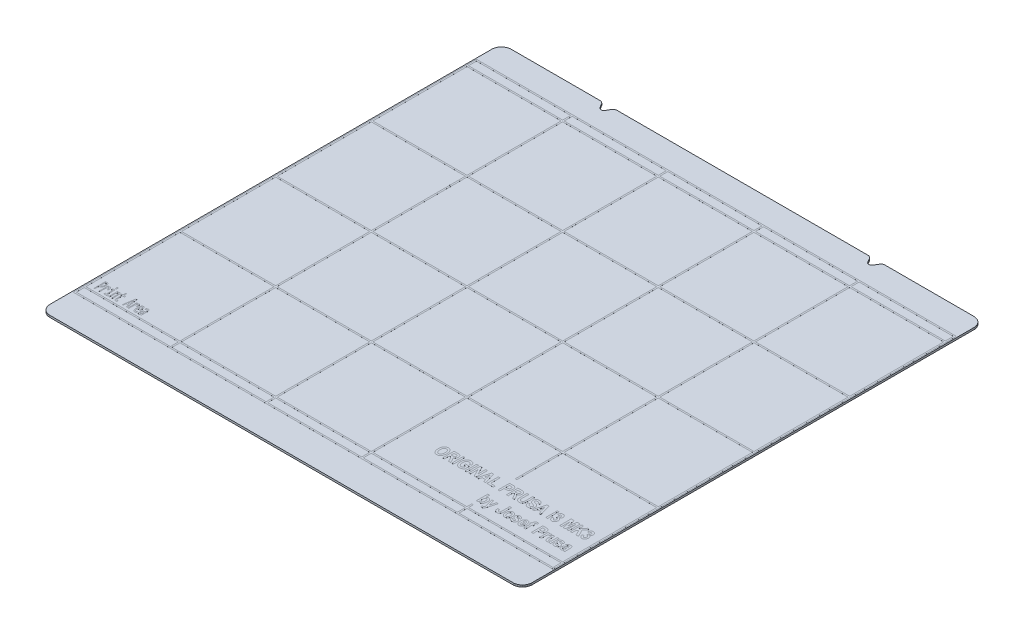
SolidWorks part; units mm, degrees
ref_plane "Front Plane" through (0, 0, 0) normal (0, 0, 1) x (1, 0, 0)
ref_plane "Top Plane" through (0, 0, 0) normal (0, 1, 0) x (1, 0, 0)
ref_plane "Right Plane" through (0, 0, 0) normal (1, 0, 0) x (0, 0, -1)
sketch "Sketch4" plane through (0, 0, 0) normal (0, 1, 0) x (1, 0, 0)
  line L0 (1.1424, 227.1088) -> (1.1396, 17.3082)
  line L1 (251.1473, 227.1078) -> (1.1424, 227.1088)
  line L2 (251.1473, 222.1039) -> (1.1479, 222.1039)
  line L3 (251.1488, 17.1042) -> (1.1424, 17.1042)
  line L4 (251.1488, 22.1065) -> (1.1424, 22.1065)
  line L5 (251.1473, 172.1058) -> (1.1479, 172.1058)
  line L6 (1.1479, 122.1039) -> (251.1473, 122.1039)
  line L7 (251.1488, 72.106) -> (1.1424, 72.106)
  line L8 (101.1481, 227.1078) -> (101.1481, 17.107)
  line L9 (51.1485, 227.1078) -> (51.1485, 17.3082)
  line L10 (151.1473, 17.107) -> (151.1473, 227.1078)
  line L11 (251.1488, 17.1042) -> (251.1473, 227.1078)
  line L12 (201.1482, 17.107) -> (201.1482, 227.1078)
  line L13 (192.2734, 231.2596) -> (192.2734, 234.381)
  line L14 (192.2734, 232.821) -> (194.3544, 232.821)
  line L15 (194.3544, 234.381) -> (194.3544, 231.2596)
  line L16 (196.9752, 231.2596) -> (195.9348, 231.2596)
  line L17 (195.9348, 231.2596) -> (195.4157, 231.7821)
  line L18 (195.4157, 231.7821) -> (195.4157, 232.821)
  line L19 (195.4157, 232.821) -> (195.9348, 233.3417)
  line L20 (195.9348, 233.3417) -> (196.9752, 233.3417)
  line L21 (196.9752, 233.3417) -> (197.4962, 232.821)
  line L22 (197.4962, 232.821) -> (197.4962, 232.3013)
  line L23 (197.4962, 232.3013) -> (195.4157, 232.3013)
  line L24 (199.0771, 233.3417) -> (200.1175, 233.3417)
  line L25 (200.1175, 233.3417) -> (200.6366, 232.821)
  line L26 (200.6366, 232.821) -> (200.6366, 231.2596)
  line L27 (200.6366, 231.2596) -> (199.0771, 231.2596)
  line L28 (199.0771, 231.2596) -> (198.5561, 231.7821)
  line L29 (198.5561, 231.7821) -> (199.0771, 232.3013)
  line L30 (199.0771, 232.3013) -> (200.6366, 232.3013)
  line L31 (202.2175, 233.8614) -> (202.2175, 231.7821)
  line L32 (202.2175, 231.7821) -> (202.7382, 231.2596)
  line L33 (201.6978, 233.3417) -> (202.7382, 233.3417)
  line L34 (203.7913, 234.381) -> (203.7913, 231.2596)
  line L35 (203.7913, 231.2596) -> (205.3526, 231.2596)
  line L36 (205.3526, 231.2596) -> (205.8718, 231.7821)
  line L37 (205.8718, 231.7821) -> (205.8718, 232.821)
  line L38 (205.8718, 232.821) -> (205.3526, 233.3417)
  line L39 (205.3526, 233.3417) -> (203.7913, 233.3417)
  line L40 (208.4931, 231.2596) -> (207.4527, 231.2596)
  line L41 (207.4527, 231.2596) -> (206.933, 231.7821)
  line L42 (206.933, 231.7821) -> (206.933, 232.821)
  line L43 (206.933, 232.821) -> (207.4527, 233.3417)
  line L44 (207.4527, 233.3417) -> (208.4931, 233.3417)
  line L45 (208.4931, 233.3417) -> (209.0138, 232.821)
  line L46 (209.0138, 232.821) -> (209.0138, 232.3013)
  line L47 (209.0138, 232.3013) -> (206.933, 232.3013)
  line L48 (212.1545, 234.381) -> (212.1545, 231.2596)
  line L49 (212.1545, 231.2596) -> (210.5947, 231.2596)
  line L50 (210.5947, 231.2596) -> (210.0735, 231.7821)
  line L51 (210.0735, 231.7821) -> (210.0735, 232.821)
  line L52 (210.0735, 232.821) -> (210.5947, 233.3417)
  line L53 (210.5947, 233.3417) -> (212.1545, 233.3417)
  line L54 (218.4367, 233.8614) -> (217.9163, 234.381)
  line L55 (217.9163, 234.381) -> (216.8759, 234.381)
  line L56 (216.8759, 234.381) -> (216.3562, 233.8614)
  line L57 (216.3562, 233.8614) -> (216.3562, 233.3417)
  line L58 (216.3562, 233.3417) -> (216.8759, 232.821)
  line L59 (216.8759, 232.821) -> (217.9163, 232.821)
  line L60 (217.9163, 232.821) -> (218.4367, 232.3013)
  line L61 (218.4367, 232.3013) -> (218.4367, 231.7821)
  line L62 (218.4367, 231.7821) -> (217.9163, 231.2596)
  line L63 (217.9163, 231.2596) -> (216.8759, 231.2596)
  line L64 (216.8759, 231.2596) -> (216.3562, 231.7821)
  line L65 (220.0176, 233.8614) -> (220.0176, 231.7821)
  line L66 (220.0176, 231.7821) -> (220.5373, 231.2596)
  line L67 (219.4966, 233.3417) -> (220.5373, 233.3417)
  line L68 (223.1514, 231.2596) -> (222.1106, 231.2596)
  line L69 (222.1106, 231.2596) -> (221.5914, 231.7821)
  line L70 (221.5914, 231.7821) -> (221.5914, 232.821)
  line L71 (221.5914, 232.821) -> (222.1106, 233.3417)
  line L72 (222.1106, 233.3417) -> (223.1514, 233.3417)
  line L73 (223.1514, 233.3417) -> (223.6721, 232.821)
  line L74 (223.6721, 232.821) -> (223.6721, 232.3013)
  line L75 (223.6721, 232.3013) -> (221.5914, 232.3013)
  line L76 (226.2932, 231.2596) -> (225.2528, 231.2596)
  line L77 (225.2528, 231.2596) -> (224.7318, 231.7821)
  line L78 (224.7318, 231.7821) -> (224.7318, 232.821)
  line L79 (224.7318, 232.821) -> (225.2528, 233.3417)
  line L80 (225.2528, 233.3417) -> (226.2932, 233.3417)
  line L81 (226.2932, 233.3417) -> (226.8129, 232.821)
  line L82 (226.8129, 232.821) -> (226.8129, 232.3013)
  line L83 (226.8129, 232.3013) -> (224.7318, 232.3013)
  line L84 (227.8736, 234.381) -> (228.3932, 234.381)
  line L85 (228.3932, 234.381) -> (228.3932, 231.2596)
  line L86 (227.8736, 231.2596) -> (228.9142, 231.2596)
  line L87 (235.1898, 233.8614) -> (234.6688, 234.381)
  line L88 (234.6688, 234.381) -> (233.6284, 234.381)
  line L89 (233.6284, 234.381) -> (233.1088, 233.8614)
  line L90 (233.1088, 233.8614) -> (233.1088, 233.3417)
  line L91 (233.1088, 233.3417) -> (233.6284, 232.821)
  line L92 (233.6284, 232.821) -> (234.6688, 232.821)
  line L93 (234.6688, 232.821) -> (235.1898, 232.3013)
  line L94 (235.1898, 232.3013) -> (235.1898, 231.7821)
  line L95 (235.1898, 231.7821) -> (234.6688, 231.2596)
  line L96 (234.6688, 231.2596) -> (233.6284, 231.2596)
  line L97 (233.6284, 231.2596) -> (233.1088, 231.7821)
  line L98 (236.2497, 234.381) -> (236.2497, 231.2596)
  line L99 (236.2497, 232.821) -> (236.7704, 233.3417)
  line L100 (236.7704, 233.3417) -> (237.8108, 233.3417)
  line L101 (237.8108, 233.3417) -> (238.3302, 232.821)
  line L102 (238.3302, 232.821) -> (238.3302, 231.2596)
  line L103 (240.9515, 231.2596) -> (239.9111, 231.2596)
  line L104 (239.9111, 231.2596) -> (239.3902, 231.7821)
  line L105 (239.3902, 231.7821) -> (239.3902, 232.821)
  line L106 (239.3902, 232.821) -> (239.9111, 233.3417)
  line L107 (239.9111, 233.3417) -> (240.9515, 233.3417)
  line L108 (240.9515, 233.3417) -> (241.4722, 232.821)
  line L109 (241.4722, 232.821) -> (241.4722, 232.3013)
  line L110 (241.4722, 232.3013) -> (239.3902, 232.3013)
  line L111 (244.0932, 231.2596) -> (243.0516, 231.2596)
  line L112 (243.0516, 231.2596) -> (242.5319, 231.7821)
  line L113 (242.5319, 231.7821) -> (242.5319, 232.821)
  line L114 (242.5319, 232.821) -> (243.0516, 233.3417)
  line L115 (243.0516, 233.3417) -> (244.0932, 233.3417)
  line L116 (244.0932, 233.3417) -> (244.6129, 232.821)
  line L117 (244.6129, 232.821) -> (244.6129, 232.3013)
  line L118 (244.6129, 232.3013) -> (242.5319, 232.3013)
  line L119 (246.1933, 233.8614) -> (246.1933, 231.7821)
  line L120 (246.1933, 231.7821) -> (246.713, 231.2596)
  line L121 (245.6726, 233.3417) -> (246.713, 233.3417)
  line L122 (10.6674, 28.2237) -> (10.9031, 28.2237)
  line L123 (29.2308, 26.2791) -> (30.7068, 26.2791)
  line L124 (28.7376, 25.7858) -> (29.2308, 26.2791)
  line L125 (29.2308, 25.2953) -> (28.7376, 25.7858)
  line L126 (30.7068, 25.2953) -> (29.2308, 25.2953)
  line L127 (30.7068, 26.7698) -> (30.7068, 25.2953)
  line L128 (30.2148, 27.2646) -> (30.7068, 26.7698)
  line L129 (29.2308, 27.2646) -> (30.2148, 27.2646)
  line L130 (27.7358, 26.2791) -> (25.7665, 26.2791)
  line L131 (27.7358, 26.7698) -> (27.7358, 26.2791)
  line L132 (27.2425, 27.2646) -> (27.7358, 26.7698)
  line L133 (26.2585, 27.2646) -> (27.2425, 27.2646)
  line L134 (25.7665, 26.7698) -> (26.2585, 27.2646)
  line L135 (25.7665, 25.7858) -> (25.7665, 26.7698)
  line L136 (26.2585, 25.2953) -> (25.7665, 25.7858)
  line L137 (27.2425, 25.2953) -> (26.2585, 25.2953)
  line L138 (24.2741, 27.2646) -> (24.7661, 27.2646)
  line L139 (23.2888, 26.2791) -> (24.2741, 27.2646)
  line L140 (23.2888, 25.2953) -> (23.2888, 27.2646)
  line L141 (20.8098, 26.2791) -> (22.287, 26.2791)
  line L142 (20.3178, 25.7858) -> (20.8098, 26.2791)
  line L143 (20.8098, 25.2953) -> (20.3178, 25.7858)
  line L144 (22.287, 25.2953) -> (20.8098, 25.2953)
  line L145 (22.287, 26.7698) -> (22.287, 25.2953)
  line L146 (21.7937, 27.2646) -> (22.287, 26.7698)
  line L147 (20.8098, 27.2646) -> (21.7937, 27.2646)
  line L148 (15.3637, 27.2646) -> (16.3491, 27.2646)
  line L149 (15.8557, 25.7858) -> (16.3491, 25.2953)
  line L150 (15.8557, 27.7551) -> (15.8557, 25.7858)
  line L151 (14.3605, 26.7698) -> (14.3605, 25.2953)
  line L152 (13.8686, 27.2646) -> (14.3605, 26.7698)
  line L153 (12.3913, 27.2646) -> (13.8686, 27.2646)
  line L154 (12.3913, 25.2953) -> (12.3913, 27.2646)
  line L155 (10.4111, 25.2953) -> (11.395, 25.2953)
  line L156 (10.9031, 27.2646) -> (10.9031, 25.2953)
  line L157 (10.4111, 27.2646) -> (10.9031, 27.2646)
  line L158 (8.9187, 27.2646) -> (9.4106, 27.2646)
  line L159 (7.9334, 26.2791) -> (8.9187, 27.2646)
  line L160 (7.9334, 25.2953) -> (7.9334, 27.2646)
  line L161 (6.4382, 26.2791) -> (4.9623, 26.2791)
  line L162 (6.9315, 26.7698) -> (6.4382, 26.2791)
  line L163 (6.9315, 27.7551) -> (6.9315, 26.7698)
  line L164 (6.4382, 28.2484) -> (6.9315, 27.7551)
  line L165 (4.9623, 28.2484) -> (6.4382, 28.2484)
  line L166 (4.9623, 25.2953) -> (4.9623, 28.2484)
  line L167 (199.8955, 5.1442) -> (199.8955, 5.3371)
  line L168 (199.8955, 5.3371) -> (199.7438, 5.9118)
  line L169 (199.7438, 5.9118) -> (199.3483, 6.4589)
  line L170 (199.3483, 6.4589) -> (198.7875, 6.7869)
  line L171 (198.7875, 6.7869) -> (198.1454, 6.8971)
  line L172 (198.1454, 6.8971) -> (197.502, 6.7869)
  line L173 (197.502, 6.7869) -> (196.9409, 6.4589)
  line L174 (196.9409, 6.4589) -> (196.5455, 5.9118)
  line L175 (196.5455, 5.9118) -> (196.3953, 5.3371)
  line L176 (196.3953, 5.3371) -> (196.3953, 5.1442)
  line L177 (196.3953, 5.1442) -> (196.3953, 4.9747)
  line L178 (196.3953, 4.9747) -> (196.5317, 4.4634)
  line L179 (196.5317, 4.4634) -> (196.9079, 3.9081)
  line L180 (196.9079, 3.9081) -> (197.4632, 3.5333)
  line L181 (197.4632, 3.5333) -> (197.9747, 3.3955)
  line L182 (197.9747, 3.3955) -> (198.1454, 3.3955)
  line L183 (198.1454, 3.3955) -> (198.3148, 3.3955)
  line L184 (198.3148, 3.3955) -> (198.8264, 3.5333)
  line L185 (198.8264, 3.5333) -> (199.3816, 3.9081)
  line L186 (199.3816, 3.9081) -> (199.7575, 4.4634)
  line L187 (199.7575, 4.4634) -> (199.8955, 4.9747)
  line L188 (199.8955, 4.9747) -> (199.8955, 5.1442)
  line L189 (54.3951, 5.1442) -> (54.3951, 5.3151)
  line L190 (54.3951, 5.3151) -> (54.2574, 5.8277)
  line L191 (54.2574, 5.8277) -> (53.8825, 6.3831)
  line L192 (53.8825, 6.3831) -> (53.3258, 6.7579)
  line L193 (53.3258, 6.7579) -> (52.8147, 6.8943)
  line L194 (52.8147, 6.8943) -> (52.6451, 6.8943)
  line L195 (52.6451, 6.8943) -> (52.4744, 6.8943)
  line L196 (52.4744, 6.8943) -> (51.9631, 6.7579)
  line L197 (51.9631, 6.7579) -> (51.4078, 6.3831)
  line L198 (51.4078, 6.3831) -> (51.0314, 5.8277)
  line L199 (51.0314, 5.8277) -> (50.8953, 5.3151)
  line L200 (50.8953, 5.3151) -> (50.8953, 5.1442)
  line L201 (50.8953, 5.1442) -> (50.8953, 4.9747)
  line L202 (50.8953, 4.9747) -> (51.0314, 4.4634)
  line L203 (51.0314, 4.4634) -> (51.4078, 3.9081)
  line L204 (51.4078, 3.9081) -> (51.9631, 3.5333)
  line L205 (51.9631, 3.5333) -> (52.4744, 3.3955)
  line L206 (52.4744, 3.3955) -> (52.6451, 3.3955)
  line L207 (52.6451, 3.3955) -> (52.8147, 3.3955)
  line L208 (52.8147, 3.3955) -> (53.3258, 3.5333)
  line L209 (53.3258, 3.5333) -> (53.8825, 3.9081)
  line L210 (53.8825, 3.9081) -> (54.2574, 4.4634)
  line L211 (54.2574, 4.4634) -> (54.3951, 4.9747)
  line L212 (54.3951, 4.9747) -> (54.3951, 5.1442)
  line L213 (0.1461, 5.1442) -> (0.1461, 4.8934)
  line L214 (0.1461, 4.8934) -> (0.2467, 4.1383)
  line L215 (0.2467, 4.1383) -> (0.5388, 3.1998)
  line L216 (0.5388, 3.1998) -> (0.9991, 2.3496)
  line L217 (0.9991, 2.3496) -> (1.6095, 1.6095)
  line L218 (1.6095, 1.6095) -> (2.3496, 0.9991)
  line L219 (2.3496, 0.9991) -> (3.1984, 0.5388)
  line L220 (3.1984, 0.5388) -> (4.1369, 0.2467)
  line L221 (4.1369, 0.2467) -> (4.8934, 0.1447)
  line L222 (4.8934, 0.1447) -> (5.1456, 0.1447)
  line L223 (247.1456, 0.1447) -> (5.1456, 0.1447)
  line L224 (247.1456, 0.1447) -> (247.3963, 0.1447)
  line L225 (247.3963, 0.1447) -> (248.1532, 0.2467)
  line L226 (248.1532, 0.2467) -> (249.0914, 0.5388)
  line L227 (249.0914, 0.5388) -> (249.9403, 0.9991)
  line L228 (249.9403, 0.9991) -> (250.6805, 1.6095)
  line L229 (250.6805, 1.6095) -> (251.2906, 2.3496)
  line L230 (251.2906, 2.3496) -> (251.7511, 3.1998)
  line L231 (251.7511, 3.1998) -> (252.0432, 4.1383)
  line L232 (252.0432, 4.1383) -> (252.145, 4.8934)
  line L233 (252.145, 4.8934) -> (252.145, 5.1442)
  line L234 (252.145, 236.1448) -> (252.145, 5.1442)
  line L235 (252.145, 236.1448) -> (252.145, 236.6244)
  line L236 (252.145, 236.6244) -> (251.7648, 238.059)
  line L237 (251.7648, 238.059) -> (250.9159, 239.4466)
  line L238 (250.9159, 239.4466) -> (250.6817, 239.6807)
  line L239 (250.6817, 239.6807) -> (250.446, 239.9165)
  line L240 (250.446, 239.9165) -> (249.0582, 240.7651)
  line L241 (249.0582, 240.7651) -> (247.6238, 241.1458)
  line L242 (247.6238, 241.1458) -> (247.1456, 241.1458)
  line L243 (0.1461, 5.1442) -> (0.1461, 236.1448)
  line L244 (5.1456, 241.1458) -> (4.6661, 241.1458)
  line L245 (4.6661, 241.1458) -> (3.2315, 240.7651)
  line L246 (3.2315, 240.7651) -> (1.8438, 239.9165)
  line L247 (1.8438, 239.9165) -> (1.6095, 239.6807)
  line L248 (1.6095, 239.6807) -> (1.3753, 239.4466)
  line L249 (1.3753, 239.4466) -> (0.5264, 238.059)
  line L250 (0.5264, 238.059) -> (0.1461, 236.6244)
  line L251 (0.1461, 236.6244) -> (0.1461, 236.1448)
  line L252 (194.8437, 237.9017) -> (194.9371, 237.7361)
  line L253 (194.9371, 237.7361) -> (195.403, 237.3394)
  line L254 (195.403, 237.3394) -> (196.1279, 237.1453)
  line L255 (196.1279, 237.1453) -> (196.8556, 237.3231)
  line L256 (196.8556, 237.3231) -> (197.3308, 237.7074)
  line L257 (197.3308, 237.7074) -> (197.4304, 237.8713)
  line L258 (54.8612, 237.8713) -> (54.959, 237.7087)
  line L259 (54.959, 237.7087) -> (55.4345, 237.3231)
  line L260 (55.4345, 237.3231) -> (56.1619, 237.1453)
  line L261 (56.1619, 237.1453) -> (56.8869, 237.3394)
  line L262 (56.8869, 237.3394) -> (57.3524, 237.7361)
  line L263 (57.3524, 237.7361) -> (57.4477, 237.9017)
  line L264 (5.1456, 241.1458) -> (51.7578, 241.1458)
  line L265 (54.8612, 237.8713) -> (53.4706, 240.1781)
  line L266 (53.4706, 240.1781) -> (53.3799, 240.3285)
  line L267 (53.3799, 240.3285) -> (52.7416, 240.888)
  line L268 (52.7416, 240.888) -> (52.0029, 241.1458)
  line L269 (52.0029, 241.1458) -> (51.7578, 241.1458)
  line L270 (57.4477, 237.9017) -> (58.7251, 240.1369)
  line L271 (60.4614, 241.1458) -> (60.2092, 241.1458)
  line L272 (60.2092, 241.1458) -> (59.4568, 240.8756)
  line L273 (59.4568, 240.8756) -> (58.8134, 240.2929)
  line L274 (58.8134, 240.2929) -> (58.7251, 240.1369)
  line L275 (194.8437, 237.9017) -> (193.566, 240.1369)
  line L276 (60.4614, 241.1458) -> (191.8299, 241.1458)
  line L277 (193.566, 240.1369) -> (193.4766, 240.2929)
  line L278 (193.4766, 240.2929) -> (192.833, 240.8756)
  line L279 (192.833, 240.8756) -> (192.0804, 241.1458)
  line L280 (192.0804, 241.1458) -> (191.8299, 241.1458)
  line L281 (200.5333, 241.1458) -> (247.1456, 241.1458)
  line L282 (197.4304, 237.8713) -> (198.8205, 240.1781)
  line L283 (200.5333, 241.1458) -> (200.2869, 241.1458)
  line L284 (200.2869, 241.1458) -> (199.548, 240.888)
  line L285 (199.548, 240.888) -> (198.9102, 240.3285)
  line L286 (198.9102, 240.3285) -> (198.8205, 240.1781)
extrude "Boss-Extrude2" add sketch "Sketch4" along normal blind 1 contours L223 L222 L221 L220 L219 L218 L217 L216 L215 L214 L213 L243 L251 L250 L249 L248 L247 L246 L245 L244 L264 L269 L268 L267 L266 L265 L258 L259 L260 L261 L262 L263 L270 L274 L273 L272 L271 L276 L280 L279 L278 L277 L275 L252 L253 L254 L255 L256 L257 L282 L286 L285 L284 L283 L281 L242 L241 L240 L239 L238 L237 L236 L235 L234 L233 L232 L231 L230 L229 L228 L227 L226 L225 L224
sketch "Sketch6" plane through (0, 1, 1) normal (0, 1, 0) x (1, 0, 0)
  line L0 (1.1424, 228.1088) -> (1.1396, 18.3082) construction
  line L1 (251.1473, 228.1078) -> (1.1424, 228.1088) construction
  line L2 (200.7482, 48.7971) -> (200.7482, 72.706)
  line L3 (251.1488, 18.1042) -> (1.1424, 18.1042) construction
  line L4 (251.1488, 23.1065) -> (1.1424, 23.1065) construction
  line L5 (151.5473, 173.5058) -> (151.5473, 222.7039)
  line L6 (1.1479, 123.1039) -> (151.1473, 123.1039) construction
  line L7 (251.1488, 73.106) -> (1.1424, 73.106) construction
  line L8 (100.7481, 227.7084) -> (51.5485, 227.7086)
  line L9 (100.7481, 223.5039) -> (51.5485, 223.5039)
  line L10 (151.1473, 18.107) -> (151.1473, 73.106) construction
  line L11 (251.1488, 18.1042) -> (251.1473, 228.1078) construction
  line L12 (201.1482, 18.107) -> (201.1482, 73.106) construction
  line L13 (192.2734, 232.2596) -> (192.2734, 235.381)
  line L14 (192.2734, 233.821) -> (194.3544, 233.821)
  line L15 (194.3544, 235.381) -> (194.3544, 232.2596)
  line L16 (196.9752, 232.2596) -> (195.9348, 232.2596)
  line L17 (195.9348, 232.2596) -> (195.4157, 232.7821)
  line L18 (195.4157, 232.7821) -> (195.4157, 233.821)
  line L19 (195.4157, 233.821) -> (195.9348, 234.3417)
  line L20 (195.9348, 234.3417) -> (196.9752, 234.3417)
  line L21 (196.9752, 234.3417) -> (197.4962, 233.821)
  line L22 (197.4962, 233.821) -> (197.4962, 233.3013)
  line L23 (197.4962, 233.3013) -> (195.4157, 233.3013)
  line L24 (199.0771, 234.3417) -> (200.1175, 234.3417)
  line L25 (200.1175, 234.3417) -> (200.6366, 233.821)
  line L26 (200.6366, 233.821) -> (200.6366, 232.2596)
  line L27 (200.6366, 232.2596) -> (199.0771, 232.2596)
  line L28 (199.0771, 232.2596) -> (198.5561, 232.7821)
  line L29 (198.5561, 232.7821) -> (199.0771, 233.3013)
  line L30 (199.0771, 233.3013) -> (200.6366, 233.3013)
  line L31 (202.2175, 234.8614) -> (202.2175, 232.7821)
  line L32 (202.2175, 232.7821) -> (202.7382, 232.2596)
  line L33 (201.6978, 234.3417) -> (202.7382, 234.3417)
  line L34 (203.7913, 235.381) -> (203.7913, 232.2596)
  line L35 (203.7913, 232.2596) -> (205.3526, 232.2596)
  line L36 (205.3526, 232.2596) -> (205.8718, 232.7821)
  line L37 (205.8718, 232.7821) -> (205.8718, 233.821)
  line L38 (205.8718, 233.821) -> (205.3526, 234.3417)
  line L39 (205.3526, 234.3417) -> (203.7913, 234.3417)
  line L40 (208.4931, 232.2596) -> (207.4527, 232.2596)
  line L41 (207.4527, 232.2596) -> (206.933, 232.7821)
  line L42 (206.933, 232.7821) -> (206.933, 233.821)
  line L43 (206.933, 233.821) -> (207.4527, 234.3417)
  line L44 (207.4527, 234.3417) -> (208.4931, 234.3417)
  line L45 (208.4931, 234.3417) -> (209.0138, 233.821)
  line L46 (209.0138, 233.821) -> (209.0138, 233.3013)
  line L47 (209.0138, 233.3013) -> (206.933, 233.3013)
  line L48 (212.1545, 235.381) -> (212.1545, 232.2596)
  line L49 (212.1545, 232.2596) -> (210.5947, 232.2596)
  line L50 (210.5947, 232.2596) -> (210.0735, 232.7821)
  line L51 (210.0735, 232.7821) -> (210.0735, 233.821)
  line L52 (210.0735, 233.821) -> (210.5947, 234.3417)
  line L53 (210.5947, 234.3417) -> (212.1545, 234.3417)
  line L54 (218.4367, 234.8614) -> (217.9163, 235.381)
  line L55 (217.9163, 235.381) -> (216.8759, 235.381)
  line L56 (216.8759, 235.381) -> (216.3562, 234.8614)
  line L57 (216.3562, 234.8614) -> (216.3562, 234.3417)
  line L58 (216.3562, 234.3417) -> (216.8759, 233.821)
  line L59 (216.8759, 233.821) -> (217.9163, 233.821)
  line L60 (217.9163, 233.821) -> (218.4367, 233.3013)
  line L61 (218.4367, 233.3013) -> (218.4367, 232.7821)
  line L62 (218.4367, 232.7821) -> (217.9163, 232.2596)
  line L63 (217.9163, 232.2596) -> (216.8759, 232.2596)
  line L64 (216.8759, 232.2596) -> (216.3562, 232.7821)
  line L65 (220.0176, 234.8614) -> (220.0176, 232.7821)
  line L66 (220.0176, 232.7821) -> (220.5373, 232.2596)
  line L67 (219.4966, 234.3417) -> (220.5373, 234.3417)
  line L68 (223.1514, 232.2596) -> (222.1106, 232.2596)
  line L69 (222.1106, 232.2596) -> (221.5914, 232.7821)
  line L70 (221.5914, 232.7821) -> (221.5914, 233.821)
  line L71 (221.5914, 233.821) -> (222.1106, 234.3417)
  line L72 (222.1106, 234.3417) -> (223.1514, 234.3417)
  line L73 (223.1514, 234.3417) -> (223.6721, 233.821)
  line L74 (223.6721, 233.821) -> (223.6721, 233.3013)
  line L75 (223.6721, 233.3013) -> (221.5914, 233.3013)
  line L76 (226.2932, 232.2596) -> (225.2528, 232.2596)
  line L77 (225.2528, 232.2596) -> (224.7318, 232.7821)
  line L78 (224.7318, 232.7821) -> (224.7318, 233.821)
  line L79 (224.7318, 233.821) -> (225.2528, 234.3417)
  line L80 (225.2528, 234.3417) -> (226.2932, 234.3417)
  line L81 (226.2932, 234.3417) -> (226.8129, 233.821)
  line L82 (226.8129, 233.821) -> (226.8129, 233.3013)
  line L83 (226.8129, 233.3013) -> (224.7318, 233.3013)
  line L84 (227.8736, 235.381) -> (228.3932, 235.381)
  line L85 (228.3932, 235.381) -> (228.3932, 232.2596)
  line L86 (227.8736, 232.2596) -> (228.9142, 232.2596)
  line L87 (235.1898, 234.8614) -> (234.6688, 235.381)
  line L88 (234.6688, 235.381) -> (233.6284, 235.381)
  line L89 (233.6284, 235.381) -> (233.1088, 234.8614)
  line L90 (233.1088, 234.8614) -> (233.1088, 234.3417)
  line L91 (233.1088, 234.3417) -> (233.6284, 233.821)
  line L92 (233.6284, 233.821) -> (234.6688, 233.821)
  line L93 (234.6688, 233.821) -> (235.1898, 233.3013)
  line L94 (235.1898, 233.3013) -> (235.1898, 232.7821)
  line L95 (235.1898, 232.7821) -> (234.6688, 232.2596)
  line L96 (234.6688, 232.2596) -> (233.6284, 232.2596)
  line L97 (233.6284, 232.2596) -> (233.1088, 232.7821)
  line L98 (236.2497, 235.381) -> (236.2497, 232.2596)
  line L99 (236.2497, 233.821) -> (236.7704, 234.3417)
  line L100 (236.7704, 234.3417) -> (237.8108, 234.3417)
  line L101 (237.8108, 234.3417) -> (238.3302, 233.821)
  line L102 (238.3302, 233.821) -> (238.3302, 232.2596)
  line L103 (240.9515, 232.2596) -> (239.9111, 232.2596)
  line L104 (239.9111, 232.2596) -> (239.3902, 232.7821)
  line L105 (239.3902, 232.7821) -> (239.3902, 233.821)
  line L106 (239.3902, 233.821) -> (239.9111, 234.3417)
  line L107 (239.9111, 234.3417) -> (240.9515, 234.3417)
  line L108 (240.9515, 234.3417) -> (241.4722, 233.821)
  line L109 (241.4722, 233.821) -> (241.4722, 233.3013)
  line L110 (241.4722, 233.3013) -> (239.3902, 233.3013)
  line L111 (244.0932, 232.2596) -> (243.0516, 232.2596)
  line L112 (243.0516, 232.2596) -> (242.5319, 232.7821)
  line L113 (242.5319, 232.7821) -> (242.5319, 233.821)
  line L114 (242.5319, 233.821) -> (243.0516, 234.3417)
  line L115 (243.0516, 234.3417) -> (244.0932, 234.3417)
  line L116 (244.0932, 234.3417) -> (244.6129, 233.821)
  line L117 (244.6129, 233.821) -> (244.6129, 233.3013)
  line L118 (244.6129, 233.3013) -> (242.5319, 233.3013)
  line L119 (246.1933, 234.8614) -> (246.1933, 232.7821)
  line L120 (246.1933, 232.7821) -> (246.713, 232.2596)
  line L121 (245.6726, 234.3417) -> (246.713, 234.3417)
  line L122 (10.6674, 29.2237) -> (10.9031, 29.2237)
  line L123 (29.2308, 27.2791) -> (30.7068, 27.2791)
  line L124 (28.7376, 26.7858) -> (29.2308, 27.2791)
  line L125 (29.2308, 26.2953) -> (28.7376, 26.7858)
  line L126 (30.7068, 26.2953) -> (29.2308, 26.2953)
  line L127 (30.7068, 27.7698) -> (30.7068, 26.2953)
  line L128 (30.2148, 28.2646) -> (30.7068, 27.7698)
  line L129 (29.2308, 28.2646) -> (30.2148, 28.2646)
  line L130 (27.7358, 27.2791) -> (25.7665, 27.2791)
  line L131 (27.7358, 27.7698) -> (27.7358, 27.2791)
  line L132 (27.2425, 28.2646) -> (27.7358, 27.7698)
  line L133 (26.2585, 28.2646) -> (27.2425, 28.2646)
  line L134 (25.7665, 27.7698) -> (26.2585, 28.2646)
  line L135 (25.7665, 26.7858) -> (25.7665, 27.7698)
  line L136 (26.2585, 26.2953) -> (25.7665, 26.7858)
  line L137 (27.2425, 26.2953) -> (26.2585, 26.2953)
  line L138 (24.2741, 28.2646) -> (24.7661, 28.2646)
  line L139 (23.2888, 27.2791) -> (24.2741, 28.2646)
  line L140 (23.2888, 26.2953) -> (23.2888, 28.2646)
  line L141 (20.8098, 27.2791) -> (22.287, 27.2791)
  line L142 (20.3178, 26.7858) -> (20.8098, 27.2791)
  line L143 (20.8098, 26.2953) -> (20.3178, 26.7858)
  line L144 (22.287, 26.2953) -> (20.8098, 26.2953)
  line L145 (22.287, 27.7698) -> (22.287, 26.2953)
  line L146 (21.7937, 28.2646) -> (22.287, 27.7698)
  line L147 (20.8098, 28.2646) -> (21.7937, 28.2646)
  line L148 (15.3637, 28.2646) -> (16.3491, 28.2646)
  line L149 (15.8557, 26.7858) -> (16.3491, 26.2953)
  line L150 (15.8557, 28.7551) -> (15.8557, 26.7858)
  line L151 (14.3605, 27.7698) -> (14.3605, 26.2953)
  line L152 (13.8686, 28.2646) -> (14.3605, 27.7698)
  line L153 (12.3913, 28.2646) -> (13.8686, 28.2646)
  line L154 (12.3913, 26.2953) -> (12.3913, 28.2646)
  line L155 (10.4111, 26.2953) -> (11.395, 26.2953)
  line L156 (10.9031, 28.2646) -> (10.9031, 26.2953)
  line L157 (10.4111, 28.2646) -> (10.9031, 28.2646)
  line L158 (8.9187, 28.2646) -> (9.4106, 28.2646)
  line L159 (7.9334, 27.2791) -> (8.9187, 28.2646)
  line L160 (7.9334, 26.2953) -> (7.9334, 28.2646)
  line L161 (6.4382, 27.2791) -> (4.9623, 27.2791)
  line L162 (6.9315, 27.7698) -> (6.4382, 27.2791)
  line L163 (6.9315, 28.7551) -> (6.9315, 27.7698)
  line L164 (6.4382, 29.2484) -> (6.9315, 28.7551)
  line L165 (4.9623, 29.2484) -> (6.4382, 29.2484)
  line L166 (4.9623, 26.2953) -> (4.9623, 29.2484)
  line L287 (0.7424, 228.5088) -> (0.7396, 18.3082)
  line L288 (251.5473, 228.5077) -> (0.7424, 228.5088)
  line L289 (251.5489, 17.7042) -> (251.5473, 228.5077)
  line L290 (251.5489, 17.7042) -> (1.1424, 17.7042)
  line L291 (250.7488, 22.7065) -> (201.5482, 22.7065)
  line L292 (51.5485, 227.7086) -> (51.5485, 223.5039)
  line L293 (101.5481, 227.7084) -> (101.5481, 223.5039)
  line L294 (251.1488, 72.706) -> (251.1485, 72.706)
  line L295 (150.7473, 18.5042) -> (150.7473, 22.7065)
  line L296 (200.7482, 18.5042) -> (200.7482, 22.7065)
  line L297 (1.541, 123.5039) -> (50.7485, 123.5039)
  line L298 (250.7477, 172.7058) -> (201.5482, 172.7058)
  line L299 (250.7474, 222.7039) -> (201.5482, 222.7039)
  line L300 (1.5424, 227.7088) -> (1.5423, 223.5039)
  line L301 (250.7473, 227.7078) -> (201.5482, 227.708)
  line L302 (250.7488, 18.5042) -> (250.7488, 22.7065)
  line L303 (250.7488, 18.5042) -> (201.5482, 18.5042)
  line L304 (250.7488, 23.5065) -> (201.5482, 23.5065)
  line L305 (50.7485, 227.7086) -> (50.7485, 223.5039)
  line L306 (100.7481, 227.7084) -> (100.7481, 223.5039)
  line L307 (251.1488, 73.506) -> (251.1484, 73.506)
  line L308 (151.5473, 18.5042) -> (151.5473, 22.7065)
  line L309 (201.5482, 18.5042) -> (201.5482, 22.7065)
  line L310 (1.541, 122.7039) -> (50.7485, 122.7039)
  line L311 (250.7477, 173.5058) -> (201.5482, 173.5058)
  line L312 (250.7474, 223.5039) -> (201.5482, 223.504)
  line L313 (0.7396, 18.3082) -> (0.7396, 17.7042)
  line L314 (0.7396, 17.7042) -> (1.1424, 17.7042)
  line L315 (1.5397, 22.7065) -> (1.5396, 18.5042)
  line L316 (50.7485, 18.5042) -> (1.5396, 18.5042)
  line L317 (1.5424, 227.7088) -> (1.5396, 18.3082) construction
  line L318 (251.1488, 22.7065) -> (1.1424, 22.7065) construction
  line L319 (251.1488, 23.5065) -> (1.1424, 23.5065) construction
  line L320 (250.7488, 18.5042) -> (1.1424, 18.5042) construction
  line L321 (50.7485, 22.7065) -> (1.5397, 22.7065)
  line L322 (101.5481, 222.7039) -> (101.5481, 173.5058)
  line L323 (150.7473, 227.7082) -> (101.5481, 227.7084)
  line L324 (51.5485, 22.7065) -> (51.5485, 18.5042)
  line L325 (50.7485, 23.5065) -> (1.5397, 23.5065)
  line L326 (50.7485, 22.7065) -> (50.7485, 18.5042)
  line L327 (100.7481, 23.5065) -> (51.5485, 23.5065)
  line L328 (100.7481, 22.7065) -> (100.7481, 18.5042)
  line L329 (100.7481, 22.7065) -> (51.5485, 22.7065)
  line L330 (200.7482, 227.708) -> (151.5473, 227.7082)
  line L331 (101.5481, 22.7065) -> (101.5481, 18.5042)
  line L332 (100.7481, 18.5042) -> (51.5485, 18.5042)
  line L333 (151.5473, 223.5039) -> (151.5473, 227.7082)
  line L334 (150.7473, 18.5042) -> (101.5481, 18.5042)
  line L335 (150.7473, 23.5065) -> (150.7473, 72.706)
  line L336 (151.5473, 18.107) -> (151.5473, 228.1078) construction
  line L337 (150.7473, 18.107) -> (150.7473, 228.1078) construction
  line L338 (150.7473, 23.5065) -> (101.5481, 23.5065)
  line L339 (151.5473, 23.5065) -> (151.5473, 72.706)
  line L340 (150.7473, 22.7065) -> (101.5481, 22.7065)
  line L341 (200.7482, 18.5042) -> (151.5473, 18.5042)
  line L342 (200.7482, 23.5065) -> (151.5473, 23.5065)
  line L343 (200.7482, 18.107) -> (200.7482, 228.1078) construction
  line L344 (201.5482, 18.107) -> (201.5482, 228.1078) construction
  line L345 (200.7482, 23.5065) -> (200.7482, 26.0065)
  line L346 (200.7482, 22.7065) -> (151.5473, 22.7065)
  line L347 (201.5482, 23.5065) -> (201.5482, 26.0065)
  line L348 (250.7488, 23.5065) -> (250.7485, 72.706)
  line L349 (250.7484, 73.506) -> (201.5482, 73.506)
  line L350 (250.7488, 18.5042) -> (250.7473, 227.7078) construction
  line L351 (250.7484, 73.506) -> (250.7481, 122.7039)
  line L352 (251.1488, 73.506) -> (1.1424, 73.506) construction
  line L353 (250.7485, 72.706) -> (201.5482, 72.706)
  line L354 (200.7482, 73.506) -> (151.5473, 73.506)
  line L355 (251.1488, 72.706) -> (1.1424, 72.706) construction
  line L356 (201.5482, 73.506) -> (201.5482, 122.7039)
  line L357 (200.7482, 72.706) -> (151.5473, 72.706)
  line L358 (200.7482, 73.506) -> (200.7482, 122.7039)
  line L359 (150.7473, 73.506) -> (150.7473, 122.7039)
  line L360 (150.7473, 73.506) -> (101.5481, 73.506)
  line L361 (151.5473, 73.506) -> (151.5473, 122.7039)
  line L362 (150.7473, 72.706) -> (101.5481, 72.706)
  line L363 (101.5481, 72.706) -> (101.5481, 23.5065)
  line L364 (100.7481, 73.506) -> (51.5485, 73.506)
  line L365 (100.7481, 72.706) -> (100.7481, 23.5065)
  line L366 (100.7481, 72.706) -> (51.5485, 72.706)
  line L367 (51.5485, 72.706) -> (51.5485, 23.5065)
  line L368 (50.7485, 73.506) -> (1.5404, 73.506)
  line L369 (50.7485, 72.706) -> (50.7485, 23.5065)
  line L370 (50.7485, 72.706) -> (1.5404, 72.706)
  line L371 (1.5404, 72.706) -> (1.5397, 23.5065)
  line L372 (1.541, 122.7039) -> (1.5404, 73.506)
  line L373 (1.1479, 123.5039) -> (251.1473, 123.5039) construction
  line L374 (51.5485, 123.5039) -> (100.7481, 123.5039)
  line L375 (1.1479, 122.7039) -> (251.1473, 122.7039) construction
  line L376 (50.7485, 122.7039) -> (50.7485, 73.506)
  line L377 (51.5485, 122.7039) -> (100.7481, 122.7039)
  line L378 (51.5485, 122.7039) -> (51.5485, 73.506)
  line L379 (101.5481, 123.5039) -> (150.7473, 123.5039)
  line L380 (101.5481, 122.7039) -> (101.5481, 73.506)
  line L381 (101.5481, 122.7039) -> (150.7473, 122.7039)
  line L382 (100.7481, 122.7039) -> (100.7481, 73.506)
  line L383 (150.7473, 123.5039) -> (150.7473, 172.7058)
  line L384 (151.5473, 122.7039) -> (200.7482, 122.7039)
  line L385 (151.1473, 122.7039) -> (151.1473, 123.1039) construction
  line L386 (151.1473, 18.107) -> (151.1473, 228.1078) construction
  line L387 (151.5473, 123.5039) -> (151.5473, 172.7058)
  line L388 (200.7482, 123.1039) -> (201.5482, 123.1039) construction
  line L389 (1.1479, 123.1039) -> (251.1473, 123.1039) construction
  line L390 (151.5473, 123.5039) -> (200.7482, 123.5039)
  line L391 (101.5481, 172.7058) -> (101.5481, 123.5039)
  line L392 (201.5482, 123.5039) -> (250.7481, 123.5039)
  line L393 (201.5482, 123.5039) -> (201.5482, 172.7058)
  line L394 (200.7482, 223.5039) -> (151.5473, 223.5039)
  line L395 (201.5482, 122.7039) -> (250.7481, 122.7039)
  line L396 (201.1482, 122.7039) -> (201.1482, 123.1039) construction
  line L397 (201.1482, 18.107) -> (201.1482, 228.1078) construction
  line L398 (200.7482, 123.5039) -> (200.7482, 172.7058)
  line L399 (250.7481, 123.5039) -> (250.7477, 172.7058)
  line L400 (150.7473, 173.5058) -> (150.7473, 222.7039)
  line L401 (51.5485, 172.7058) -> (51.5485, 123.5039)
  line L402 (150.7473, 173.5058) -> (101.5481, 173.5058)
  line L403 (250.7477, 173.5058) -> (250.7474, 222.7039)
  line L404 (201.5482, 173.5058) -> (201.5482, 222.7039)
  line L405 (200.7482, 173.5058) -> (151.5473, 173.5058)
  line L406 (250.7474, 223.5039) -> (250.7473, 227.7078)
  line L407 (200.7482, 173.5058) -> (200.7482, 222.7039)
  line L408 (51.1485, 123.1039) -> (51.1485, 18.3082) construction
  line L409 (200.7482, 172.7058) -> (151.5473, 172.7058)
  line L410 (150.7473, 172.7058) -> (101.5481, 172.7058)
  line L411 (100.7481, 173.5058) -> (51.5485, 173.5058)
  line L412 (50.7485, 173.5058) -> (1.5417, 173.5058)
  line L413 (150.7473, 223.5039) -> (101.5481, 223.5039)
  line L414 (100.7481, 172.7058) -> (100.7481, 123.5039)
  line L415 (1.5417, 172.7058) -> (1.541, 123.5039)
  line L416 (100.7481, 172.7058) -> (51.5485, 172.7058)
  line L417 (101.1481, 123.1039) -> (101.1481, 18.107) construction
  line L418 (100.7481, 222.7039) -> (51.5485, 222.7039)
  line L419 (50.7485, 172.7058) -> (50.7485, 123.5039)
  line L420 (50.7485, 227.7086) -> (1.5424, 227.7088)
  line L421 (50.7485, 172.7058) -> (1.5417, 172.7058)
  line L422 (200.7482, 48.7971) -> (201.5482, 48.7971)
  line L424 (201.5482, 48.7971) -> (201.5482, 72.706)
  line L425 (1.5423, 222.7039) -> (1.5417, 173.5058)
  line L426 (250.7473, 227.7078) -> (1.5424, 227.7088) construction
  line L427 (50.7485, 223.5039) -> (1.5423, 223.5039)
  line L428 (50.7485, 222.7039) -> (1.5423, 222.7039)
  line L429 (51.5485, 222.7039) -> (51.5485, 173.5058)
  line L430 (50.7485, 222.7039) -> (50.7485, 173.5058)
  line L431 (150.7473, 223.5039) -> (150.7473, 227.7082)
  line L432 (100.7481, 222.7039) -> (100.7481, 173.5058)
  line L433 (150.7473, 222.7039) -> (101.5481, 222.7039)
  line L434 (201.5482, 223.504) -> (201.5482, 227.708)
  line L436 (200.7482, 223.5039) -> (200.7482, 227.708)
  line L437 (200.7482, 222.7039) -> (151.5473, 222.7039)
  line L438 (200.7482, 26.0065) -> (201.5482, 26.0065)
  point P268 (51.5485, 228.1078)
  point P269 (51.5485, 18.3082)
  point P270 (101.5481, 228.1078)
  point P271 (101.5481, 18.107)
  point P291 (50.7485, 228.1078)
  point P292 (50.7485, 18.3082)
  point P293 (100.7481, 228.1078)
  point P294 (100.7481, 18.107)
  dimension "D1" = 0.4
  dimension "D3" = 2.5
  dimension "D2" = 0.4
extrude "Boss-Extrude5" add sketch "Sketch6" along normal blind 0.01 contours L313 L314 L290 L289 L288 L287 L438 L345 L342 L339 L357 L2 L422 L424 L353 L348 L304 L347 L437 L407 L405 L5 L436 L394 L333 L330 L433 L400 L402 L322 L431 L413 L293 L323 L421 L419 L297 L415 region at (126.1449, 1, -227.1806)
sketch "Sketch7" plane through (0, 1, 0) normal (0, 1, 0) x (1, 0, 0)
  line L0 (1.5397, 23.9283) -> (50.7485, 23.9283) construction
  line L1 (1.5404, 71.706) -> (1.5397, 22.5065) construction
  line L2 (50.7485, 71.706) -> (50.7485, 22.5065) construction
  line L3 (151.5473, 38.2322) -> (250.7487, 38.2322) construction
  line L4 (151.5473, 22.5065) -> (151.5473, 71.706) construction
  line L5 (250.7488, 22.5065) -> (250.7485, 71.706) construction
  text T0 " Print Area" font "Consolas" height 6
  text T1 "<b>ORIGINAL PRUSA i3 MK3  </b>\r\n<b>by Josef Prusa </b> " font "Helvetica" height 6
extrude "Boss-Extrude6" add sketch "Sketch7" along normal blind 0.01
ref_plane "Plane1" through (126.1456, 0, 0) normal (-1, 0, 0) x (0, 0, 1)
ref_plane "Plane2" through (0, 0, -237.1453) normal (0, 0, -1) x (0, -1, 0)
